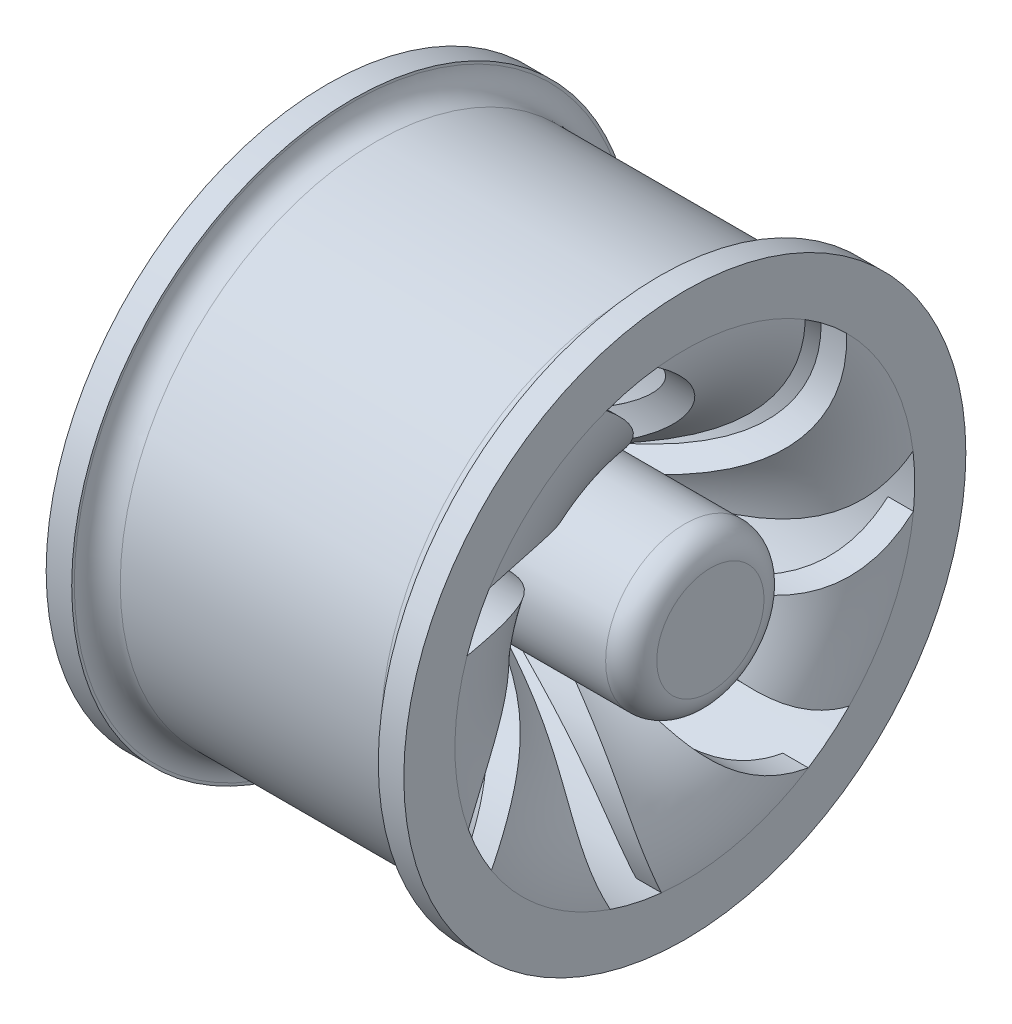
SolidWorks part; units mm, degrees
material "AISI 1020 Steel, Cold Rolled"
ref_plane "Front Plane" through (0, 0, 0) normal (0, 0, 1) x (1, 0, 0)
ref_plane "Top Plane" through (0, 0, 0) normal (0, 1, 0) x (1, 0, 0)
ref_plane "Right Plane" through (0, 0, 0) normal (1, 0, 0) x (0, 0, -1)
sketch "Sketch1" plane through (0, 0, 0) normal (0, 0, 1) x (1, 0, 0)
  line L0 (0, 0) -> (250.7524, 0) construction
  line L1 (0, 0) -> (0, 330.2935) construction
  line L2 (-177.8, 228.6) -> (152.4, 228.6)
  line L3 (177.8, 228.6) -> (177.8, 279.4)
  line L4 (177.8, 279.4) -> (152.4, 279.4)
  line L5 (152.4, 279.4) -> (152.4, 276.86)
  line L6 (129.54, 254) -> (-129.54, 254)
  line L7 (-152.4, 279.4) -> (-152.4, 276.86)
  line L8 (-177.8, 279.4) -> (-152.4, 279.4)
  line L9 (-177.8, 228.6) -> (-177.8, 279.4)
  line L10 (177.8, 192.1475) -> (177.8, 265.0525) construction
  line L11 (0, 50.8) -> (0, 78.7226)
  arc A0 (152.4, 276.86) -> (129.54, 254) centre (129.54, 276.86) cw
  arc A1 (-152.4, 276.86) -> (-129.54, 254) centre (-129.54, 276.86) ccw
  spline S0 degree 3 poles (177.8, 228.6) (177.8, 129.5835) (68.8448, 82.2726) (0, 50.8) knots 0 0 0 0 1 1 1 1
  spline S1 degree 1 poles (152.4, 228.6) (-10.5605, 73.9006) knots 0 0 1 1 construction
  spline S2 degree 3 poles (152.4, 228.6) (152.4, 227.3579) (152.3568, 224.8543) (152.1034, 220.006) (151.4834, 214.1221) (150.2816, 207.3439) (148.0964, 198.6256) (144.3126, 188.2504) (138.167, 176.4348) (130.4749, 165.1465) (118.2744, 150.7509) (99.6821, 133.9972) (77.8422, 119.0085) (59.294, 108.0664) (45.0671, 100.3619) (30.7446, 93.1309) (18.9096, 87.468) (9.6061, 83.1323) (4.3797, 80.7276) (0.9149, 79.1409) (-1.3352, 78.112) (-4.0548, 76.8704) (-7.3002, 75.3898) (-9.4706, 74.3988) (-10.5605, 73.9006) knots 0 0 0 0 0.015625 0.03125 0.0625 0.09375 0.125 0.1875 0.25 0.3125 0.375 0.5 0.625 0.6875 0.75 0.8125 0.875 0.90625 0.9375 0.946306 0.954118 0.96875 0.984375 1 1 1 1 only from (152.4, 228.6) to (0, 78.7226)
  point P4 (0, 254)
  point P12 (152.4, 254)
  point P19 (177.5842, 228.6)
  point P25 (0, 217.618)
  point P27 (0, 0)
  dimension "D5" = 22.86
  dimension "D1" = 25.4
  dimension "D2" = 50.8
  dimension "D3" = 355.6
  dimension "D4" = 25.4
  dimension "D6" = 254
  dimension "D7" = 50.8
  dimension "D8" = 127
  dimension "D9" = 25.4
revolve "Revolve1" add sketch "Sketch1" angle 360 about L0
sketch "Sketch2" plane through (-177.8, 0, 0) normal (-1, 0, 0) x (0, 0, 1)
  circle A0 centre (0, 0) radius 50.8 construction
  circle A1 centre (0, 0) radius 50.8
  circle A2 centre (0, 0) radius 78.7226 construction
  circle A3 centre (0, 0) radius 78.7226
extrude "Boss-Extrude1" add sketch "Sketch2" against normal blind 330.2
sketch "Sketch3" plane through (152.4, 0, 0) normal (1, 0, 0) x (0, 0, -1)
  circle A0 centre (0, 0) radius 78.7226 construction
  circle A1 centre (0, 0) radius 78.7226
extrude "Boss-Extrude2" add sketch "Sketch3" along normal blind 50.8
sketch "Sketch4" plane through (177.8, 0, 0) normal (1, 0, 0) x (0, 0, -1)
  circle A0 centre (0, 0) radius 78.7226 construction
  arc A1 (27.7658, 73.6635) -> (-27.7658, 73.6635) centre (0, 0) ccw
  circle A2 centre (0, 0) radius 228.6 construction
  arc A3 (-26.9903, 227.0011) -> (-77.7903, 214.9573) centre (0, 0) ccw
  spline S0 degree 2 poles (-77.7903, 214.9573) (-7.8946, 157.7849) (-27.7658, 73.6635) knots 0 0 0 1 1 1
  spline S1 degree 2 poles (27.7658, 73.6635) (55.7618, 167.9121) (-26.9903, 227.0011) knots 0 0 0 1 1 1
  dimension "3.75" = 50.8
extrude "Cut-Extrude2" cut sketch "Sketch4" against normal through all
pattern_circular "CirPattern1" count 7 over 360 about axis through (203.2, 0, 0) along (1, 0, 0) of "Cut-Extrude2"
fillet "Fillet1" radius 25.4 1 edges at (203.2, 0, -78.7226)
ref_plane "Plane1" through (0, 0, 0) normal (-1, 0, 0) x (0, 0, 1)
